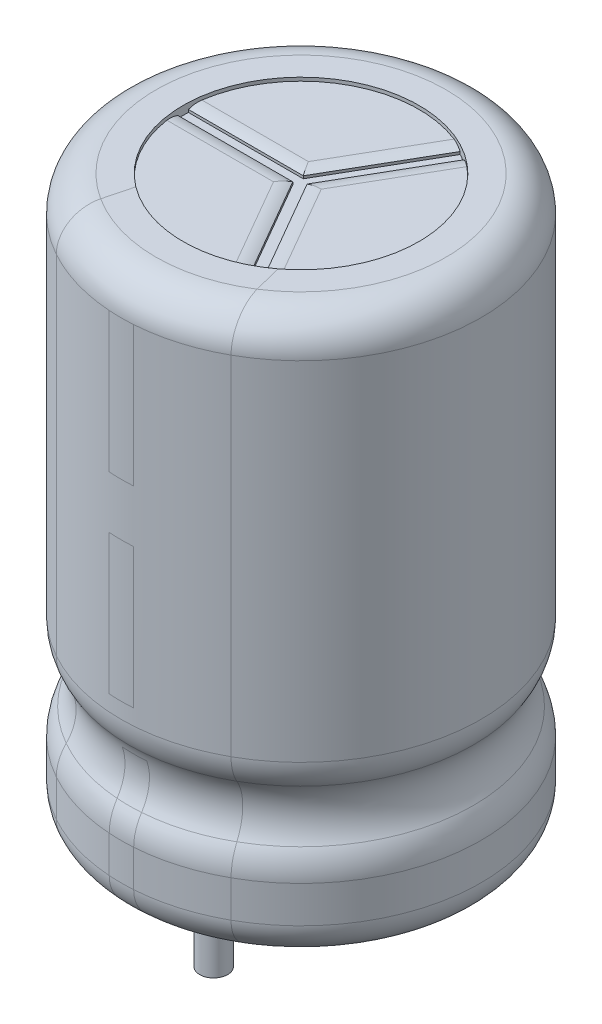
SolidWorks part; units mm, degrees
ref_plane "Front" through (0, 0, 0) normal (0, 0, 1) x (1, 0, 0)
ref_plane "Top" through (0, 0, 0) normal (0, 1, 0) x (1, 0, 0)
ref_plane "Right" through (0, 0, 0) normal (1, 0, 0) x (0, 0, -1)
sketch "Sketch1" plane through (0, 0, 0) normal (1, 0, 0) x (0, 0, -1)
  line L0 (0, 33.3732) -> (0, 0) construction
  line L1 (0, 0) -> (30.9962, 0) construction
  line L2 (0, 15.8) -> (3.375, 15.8)
  line L3 (3.375, 14.8) -> (3.375, 15.9)
  line L4 (4.15, 15.9) -> (3.375, 15.9)
  line L5 (5.15, 14.9) -> (5.15, 4.95)
  line L6 (5.15, 1.95) -> (5.15, 0.9)
  line L7 (4, -0.1) -> (4.15, -0.1)
  line L8 (4, 0) -> (4, -0.1)
  line L9 (4, 0) -> (0, 0)
  line L10 (0, 0) -> (0, 15.8)
  line L11 (0, 7.9) -> (2.9717, 7.9) construction
  line L12 (4.7, 3.45) -> (4.7, 1.4188) construction
  line L13 (0, 14.8) -> (3.375, 14.8)
  arc A0 (4.15, 15.9) -> (5.15, 14.9) centre (4.15, 14.9) cw
  arc A1 (5.15, 4.95) -> (4.925, 4.2) centre (3.7875, 4.95) cw
  arc A2 (4.925, 4.2) -> (4.925, 2.7) centre (6.0625, 3.45) ccw
  arc A3 (4.925, 2.7) -> (5.15, 1.95) centre (3.7875, 1.95) cw
  arc A4 (5.15, 0.9) -> (4.15, -0.1) centre (4.15, 0.9) cw
  dimension "D6" = 1
  dimension "D7" = 3
  dimension "D9" = 9.4
  dimension "D1" = 16
  dimension "D2" = 10.3
  dimension "D3" = 0.1
  dimension "D4" = 6.75
  dimension "D5" = 1.15
  dimension "D8" = 3.45
  dimension "D11" = 1
revolve "Revolve1" add sketch "Sketch1" angle 360 about L0 region at (0, 15.3, -1.6875)
sketch "Sketch2" plane through (0, 0, 0) normal (1, 0, 0) x (0, 0, -1)
  line L0 (0, 32.8461) -> (0, 15.8) construction
  line L1 (0, 15.8) -> (3.375, 15.8) construction
  line L4 (-0.5, 15.8) -> (0.5, 15.8)
  line L5 (0.15, 15.725) -> (0.15, 15.65)
  line L6 (-0.15, 15.65) -> (-0.15, 15.725)
  line L7 (-0.15, 15.65) -> (0.15, 15.65)
  arc A0 (0.5, 15.8) -> (0.15, 15.725) centre (0.5, 14.9458) ccw
  arc A2 (-0.15, 15.725) -> (-0.5, 15.8) centre (-0.5, 14.9458) ccw
  dimension "D2" = 0.15
  dimension "D1" = 1
  dimension "D3" = 0.3
  dimension "D4" = 0.075
extrude "Cut-Extrude1" cut sketch "Sketch2" against normal through all
pattern_circular "CirPattern1" count 3 over 360 about axis through (0, 33.3732, 0) along (0, 1, 0) of "Cut-Extrude1"
revolve "Revolve2" add sketch "Sketch1<3>" angle 360 about L0 region at (0, 7.6218, -2.5866)
sketch "Sketch1<3>" plane through (0, 0, 0) normal (1, 0, 0) x (0, 0, -1) same geometry as "Sketch1"
sketch "Sketch3" plane through (0, 15.9, 0) normal (0, 1, 0) x (1, 0, 0)
  line L0 (1.3339, 0) -> (2.5, -4.5025)
  line L1 (-1.3339, 0) -> (-2.5, -4.5025)
  line L2 (0, 0) -> (0, 5.15) construction
  line L3 (-2.5, -4.5025) -> (2.5, -4.5025) construction
  line L4 (2.5, -4.5025) -> (2.7507, -5.4706)
  line L5 (-2.5, -4.5025) -> (-2.7507, -5.4706)
  line L6 (-1.3339, 0) -> (1.3339, 0) construction
  circle A0 centre (0, 0) radius 5.15 construction
  circle A1 centre (0, 0) radius 5.15 construction
  dimension "D1" = 5
  dimension "D2" = 1
split line "Split Line1"
ref_plane "Plane1" through (0, 0, 4.5025) normal (0, 0, 1) x (1, 0, 0)
sketch "Sketch4" plane through (0, 0, 4.5025) normal (0, 0, 1) x (1, 0, 0)
  line L0 (0, 0) -> (0, 17.6301) construction
  line L1 (0.35, 10.9) -> (0.35, 9.4) construction
  line L2 (0.35, 14.9) -> (-0.35, 14.9)
  line L3 (0.35, 14.9) -> (0.35, 10.9)
  line L4 (0.35, 10.9) -> (-0.35, 10.9)
  line L6 (-0.35, 14.9) -> (-0.35, 10.9)
  line L7 (0.35, 9.4) -> (-0.35, 9.4)
  line L8 (0.35, 9.4) -> (0.35, 5.4)
  line L9 (0.35, 5.4) -> (-0.35, 5.4)
  line L10 (-0.35, 9.4) -> (-0.35, 5.4)
  line L11 (0.35, 3.9) -> (-0.35, 3.9)
  line L12 (0.35, 3.9) -> (0.35, -0.1)
  line L13 (0.35, -0.1) -> (-0.35, -0.1)
  line L14 (-0.35, 3.9) -> (-0.35, -0.1)
  line L15 (0.35, 5.4) -> (0.35, 3.9) construction
  line L16 (-2.5, 14.9) -> (2.5, 14.9) construction
  dimension "D1" = 0.7
  dimension "D2" = 4
  dimension "D3" = 1.5
split line "Split Line2"
sketch "Sketch5" plane through (0, 0, 0) normal (0, -1, 0) x (1, 0, 0)
  line L0 (0, 2.5) -> (0, 0) construction
  line L1 (0, 0) -> (2.5084, 0) construction
  circle A0 centre (0, 2.5) radius 0.4
  circle A1 centre (0, -2.5) radius 0.4
  dimension "D1" = 0.8
  dimension "D2" = 5
extrude "Boss-Extrude1" add sketch "Sketch5" along normal blind 2.5
